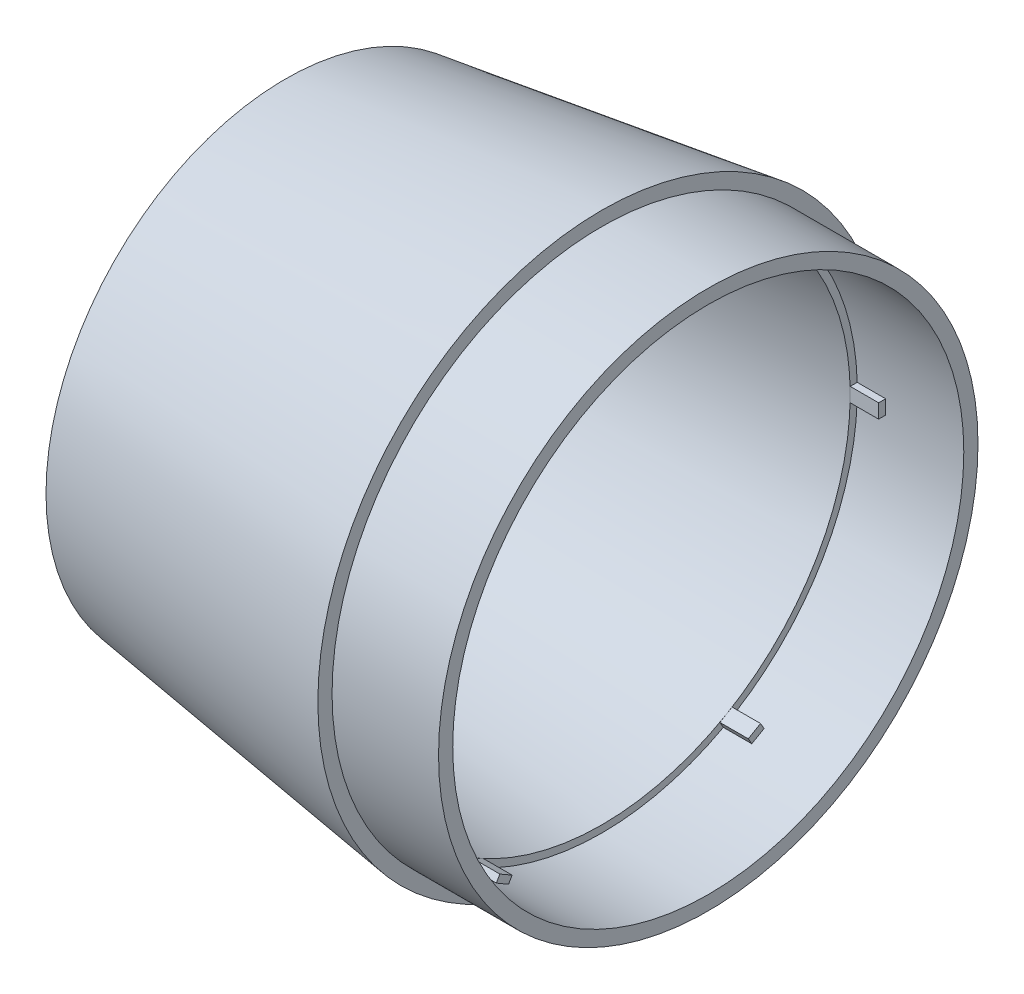
SolidWorks part; units mm, degrees
ref_plane "Ön Düzlem" through (0, 0, 0) normal (0, 0, 1) x (1, 0, 0)
ref_plane "Üst Düzlem" through (0, 0, 0) normal (0, 1, 0) x (1, 0, 0)
ref_plane "Sağ Düzlem" through (0, 0, 0) normal (1, 0, 0) x (0, 0, -1)
sketch "Çizim1" plane through (0, 0, 0) normal (0, 0, 1) x (1, 0, 0)
  line L0 (-44.5621, 33.7372) -> (-44.5621, 31.7372)
  line L1 (0, 40) -> (-44.5621, 33.7372)
  line L4 (-33.5551, 31.7372) -> (-44.5621, 31.7372)
  line L6 (15, 36) -> (15, 38)
  line L7 (-44.3163, 0) -> (0, 0)
  line L15 (0, 38) -> (15, 38)
  line L21 (0, 36) -> (15, 36)
  line L23 (0, 40) -> (0, 38)
  line L25 (-33.5551, 31.7372) -> (0, 35)
  line L26 (0, 36) -> (0, 35)
  point P4 (0, 34.8665)
  dimension "D1" = 2
  dimension "D2" = 44.3163
ref_axis "Eksen1" through (0, 0, 0) along (-1, 0, 0)
revolve "Döndür2" add sketch "Çizim1" angle 360 about L7 region at (-15.7963, 35.4536, 0)
sketch "Çizim3" plane through (0, 0, 0) normal (0, 1, 0) x (1, 0, 0)
  line L0 (0, -36) -> (15, -36) construction
  line L4 (0, -36) -> (4, -36)
  line L6 (4, -36) -> (4, -35)
  line L7 (4, -35) -> (0, -35)
  line L9 (0, -35) -> (0, -36)
  point P0 (4, -35)
  point P2 (0, -35.9363)
  dimension "D1" = 4
extrude "Yükseklik-Ekstrüzyon1" add sketch "Çizim3" along normal blind 1 and the other way blind 1
pattern_circular "Dairesel Kaplama1" count 6 over 360 about axis through (0, 0, 0) along (-1, 0, 0) of "Yükseklik-Ekstrüzyon1"
